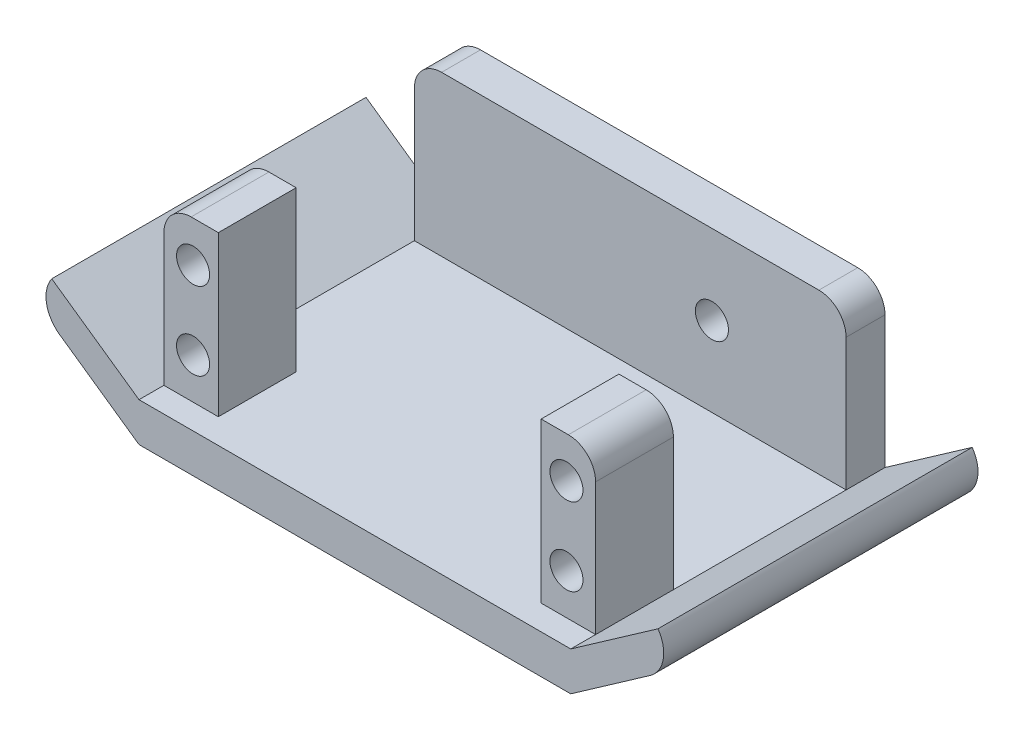
SolidWorks part; units mm, degrees
ref_plane "Front" through (0, 0, 0) normal (0, 0, 1) x (1, 0, 0)
ref_plane "Top" through (0, 0, 0) normal (0, 1, 0) x (1, 0, 0)
ref_plane "Right" through (0, 0, 0) normal (1, 0, 0) x (0, 0, -1)
sketch "Sketch1" plane through (0, 0, 0) normal (0, 1, 0) x (1, 0, 0)
  line L1 (0, 0) -> (55.5, 0)
  line L2 (0, 0) -> (0, 40.4)
  line L3 (0, 40.4) -> (55.5, 40.4)
  line L4 (55.5, 0) -> (55.5, 40.4)
  dimension "D1" = 55.5
  dimension "D2" = 40.4
extrude "base" add sketch "Sketch1" along normal blind 5
sketch "Sketch2" plane through (0, 0, -40.4) normal (0, 0, -1) x (-1, 0, 0)
  line L1 (0, 5) -> (0, 0) construction
  line L2 (-55.5, 0) -> (0, 0)
  line L3 (-55.5, 0) -> (-55.5, 25.5)
  line L4 (-55.5, 25.5) -> (0, 25.5)
  line L5 (0, 0) -> (0, 25.5)
  line L6 (-55.5, 5) -> (0, 5) construction
  dimension "D1" = 20.5
extrude "wall" add sketch "Sketch2" against normal blind 5
ref_plane "Plane1" through (0, 0, -8.2) normal (0, 0, 1) x (1, 0, 0)
sketch "Sketch3" plane through (0, 0, -8.2) normal (0, 0, 1) x (1, 0, 0)
  line L0 (0, 5) -> (55.5, 5) construction
  line L1 (0, 25.5) -> (7, 25.5)
  line L2 (0, 25.5) -> (0, 5)
  line L3 (0, 5) -> (7, 5)
  line L4 (7, 25.5) -> (7, 5)
  line L5 (27.75, 5) -> (27.75, 25.5) construction
  line L6 (55.5, 5) -> (0, 5) construction
  line L7 (0, 25.5) -> (55.5, 25.5) construction
  line L8 (55.5, 5) -> (48.5, 5)
  line L9 (48.5, 25.5) -> (48.5, 5)
  line L10 (55.5, 25.5) -> (48.5, 25.5)
  line L11 (55.5, 25.5) -> (55.5, 5)
  dimension "D1" = 7
extrude "mountingTabs" add sketch "Sketch3" along normal blind 5
sketch "Sketch4" plane through (0, 0, 0) normal (0, 0, 1) x (1, 0, 0)
  line L0 (27.75, 0) -> (27.75, 25.5) construction
  line L1 (0, 0) -> (55.5, 0) construction
  line L2 (0, 25.5) -> (55.5, 25.5) construction
  line L3 (0, 0) -> (-10.2089, 7.1483)
  line L4 (0, 5) -> (-11.2182, 12.8551)
  line L5 (0, 5) -> (0, 0)
  line L6 (55.5, 5) -> (66.7182, 12.8551)
  line L7 (55.5, 5) -> (55.5, 0)
  line L8 (55.5, 0) -> (65.7089, 7.1483)
  arc A0 (-11.2182, 12.8551) -> (-10.2089, 7.1483) centre (-7.8572, 10.5069) ccw
  arc A1 (66.7182, 12.8551) -> (65.7089, 7.1483) centre (63.3572, 10.5069) cw
  dimension "D1" = 145
  dimension "D2" = 12.4627
  dimension "D3" = 13.6949
extrude "lips" add sketch "Sketch4" against normal up to surface (40.4 mm away) up to face at (27.75, 12.75, -40.4)
sketch "Sketch5" plane through (0, 0, -3.2) normal (0, 0, 1) x (1, 0, 0)
  line L0 (27.75, 0) -> (27.75, 25.5) construction
  line L3 (0, 15.25) -> (55.5, 15.25) construction
  line L4 (0, 25.5) -> (0, 5) construction
  line L5 (55.5, 5) -> (55.5, 25.5) construction
  line L6 (7, 25.5) -> (0, 25.5) construction
  line L7 (0, 0) -> (55.5, 0) construction
  line L8 (0, 25.5) -> (55.5, 25.5) construction
  circle A0 centre (3.75, 20.25) radius 2.125
  circle A1 centre (3.75, 10.25) radius 2.125
  circle A4 centre (51.75, 10.25) radius 2.125
  circle A5 centre (51.75, 20.25) radius 2.125
  dimension "D1" = 4.25
  dimension "D2" = 5.25
  dimension "D3" = 3.75
extrude "mountingHoles" cut sketch "Sketch5" against normal blind 5
fillet "fillets" radius 3.5 4 edges at (55.5, 25.5, -37.9) (55.5, 25.5, -5.7) (0, 25.5, -37.9) (0, 25.5, -5.7)
sketch "Sketch6" plane through (0, 0, -35.4) normal (0, 0, 1) x (1, 0, 0)
  line L0 (3.5, 25.5) -> (52, 25.5) construction
  line L1 (55.5, 5) -> (55.5, 22) construction
  circle A0 centre (38.25, 15.25) radius 2.125
  dimension "D1" = 4.25
  dimension "D2" = 10.25
  dimension "D3" = 17.25
extrude "throughHole" cut sketch "Sketch6" against normal blind 5
sketch "Sketch7" plane through (0, 0, -8.2) normal (0, 0, -1) x (-1, 0, 0)
  line L4 (-48.5, 25.5) -> (-52, 25.5)
  line L5 (-55.5, 22) -> (-55.5, 5)
  line L6 (-55.5, 5) -> (-48.5, 5)
  line L7 (-48.5, 5) -> (-48.5, 25.5)
  line L8 (-48.5, 25.5) -> (-52, 25.5)
  line L9 (-55.5, 22) -> (-55.5, 5)
  line L10 (-55.5, 5) -> (-48.5, 5)
  line L11 (-48.5, 5) -> (-48.5, 25.5)
  line L12 (0, 5) -> (0, 22)
  line L13 (-3.5, 25.5) -> (-7, 25.5)
  line L14 (-7, 25.5) -> (-7, 5)
  line L15 (-7, 5) -> (0, 5)
  line L16 (0, 5) -> (0, 22)
  line L17 (-3.5, 25.5) -> (-7, 25.5)
  line L18 (-7, 25.5) -> (-7, 5)
  line L19 (-7, 5) -> (0, 5)
  circle A0 centre (-51.75, 20.25) radius 2.125 construction
  arc A1 (-52, 25.5) -> (-55.5, 22) centre (-52, 22) ccw
  arc A2 (-52, 25.5) -> (-55.5, 22) centre (-52, 22) ccw
  arc A3 (0, 22) -> (-3.5, 25.5) centre (-3.5, 22) ccw
  arc A4 (0, 22) -> (-3.5, 25.5) centre (-3.5, 22) ccw
  circle A5 centre (-51.75, 20.25) radius 2.125
  circle A6 centre (-51.75, 10.25) radius 2.125 construction
  circle A7 centre (-51.75, 10.25) radius 2.125
  circle A8 centre (-3.75, 10.25) radius 2.125 construction
  circle A9 centre (-3.75, 10.25) radius 2.125
  circle A10 centre (-3.75, 20.25) radius 2.125 construction
  circle A11 centre (-3.75, 20.25) radius 2.125
  dimension "D1" = 0
  dimension "D2" = 0
extrude "Boss-Extrude1" add sketch "Sketch7" along normal blind 5
